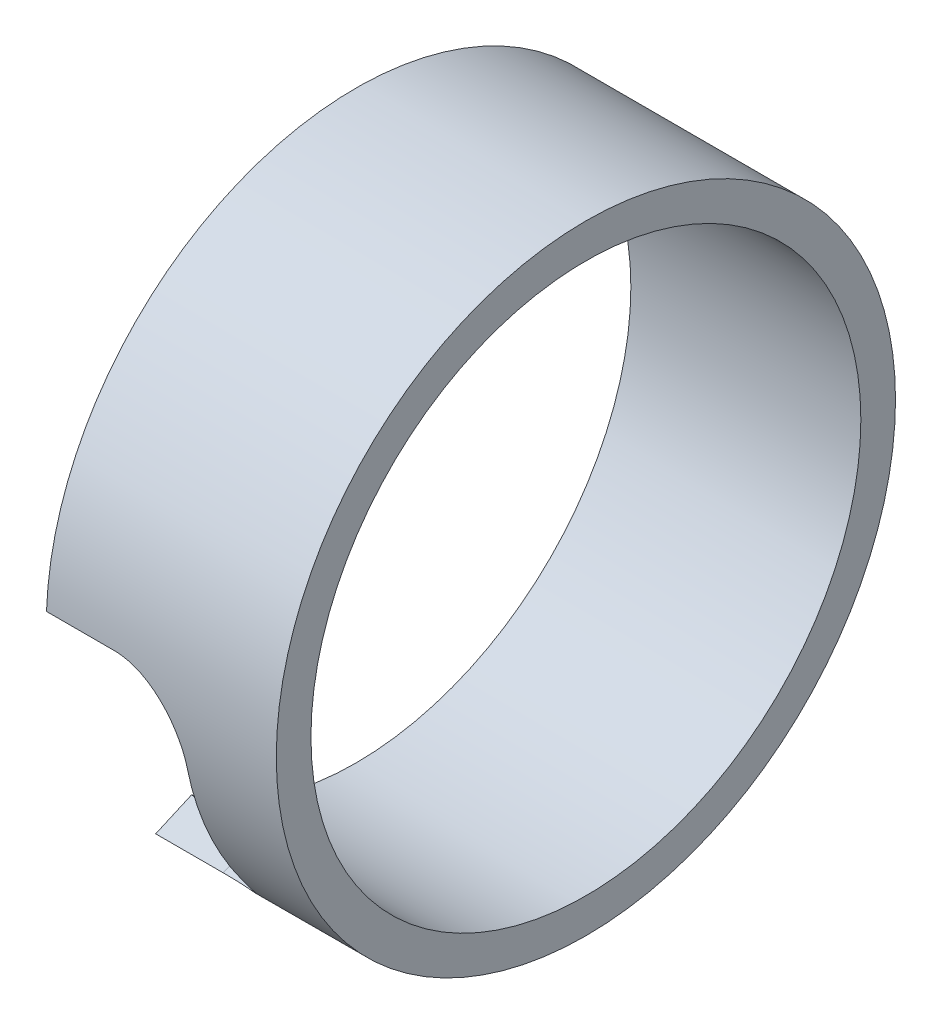
SolidWorks part; units mm, degrees
material "Nylon 6/10"
ref_plane "Front Plane" through (0, 0, 0) normal (0, 0, 1) x (1, 0, 0)
ref_plane "Top Plane" through (0, 0, 0) normal (0, 1, 0) x (1, 0, 0)
ref_plane "Right Plane" through (0, 0, 0) normal (1, 0, 0) x (0, 0, -1)
sketch "Sketch1" plane through (0, 0, 0) normal (0, 0, 1) x (1, 0, 0)
  line L0 (-31.75, 7.5) -> (-48.665, 7.5) construction
  line L1 (-45.363, 8.7312) -> (-38.877, 8.7312)
  line L2 (-45.363, 8.7312) -> (-45.363, 7.754)
  line L3 (-45.363, 7.754) -> (-38.877, 7.754)
  line L4 (-38.877, 8.7312) -> (-38.877, 7.754)
  line L5 (-45.49, -7.7612) -> (-45.49, -1.9392) construction
  line L6 (-38.75, 15.2446) -> (-38.75, -15.2446) construction
  line L7 (0, 0) -> (-47.1489, 0) construction
  dimension "D1" = 0.254
  dimension "D2" = 0.127
  dimension "D3" = 0.127
  dimension "D4" = 17.4625
revolve "Revolve1" add sketch "Sketch1" angle 360 about L7
ref_plane "Plane1" through (0, 0, 0) normal (0, -0.404, 0.9147) x (1, 0, 0)
sketch "Sketch3" plane through (0, 0, 0) normal (0, -0.404, 0.9147) x (1, 0, 0)
  line L0 (-45.363, 3.81) -> (-45.363, -3.81)
  line L1 (-45.363, 7.754) -> (-45.363, -7.754) construction
  line L2 (-45.363, -3.81) -> (-43.458, -3.81)
  line L3 (-41.553, -1.905) -> (-41.553, 1.905)
  line L4 (-43.458, 3.81) -> (-45.363, 3.81)
  line L5 (-45.363, 8.7313) -> (-45.363, -8.7312) construction
  line L6 (-45.363, 8.7313) -> (-45.363, -8.7312) construction
  line L7 (-41.553, 0) -> (-45.363, 0) construction
  arc A0 (-43.458, -3.81) -> (-41.553, -1.905) centre (-43.458, -1.905) ccw
  arc A1 (-41.553, 1.905) -> (-43.458, 3.81) centre (-43.458, 1.905) ccw
  dimension "D1" = 7.62
  dimension "D2" = 3.81
extrude "Cut-Extrude1" cut sketch "Sketch3" along normal up to next
